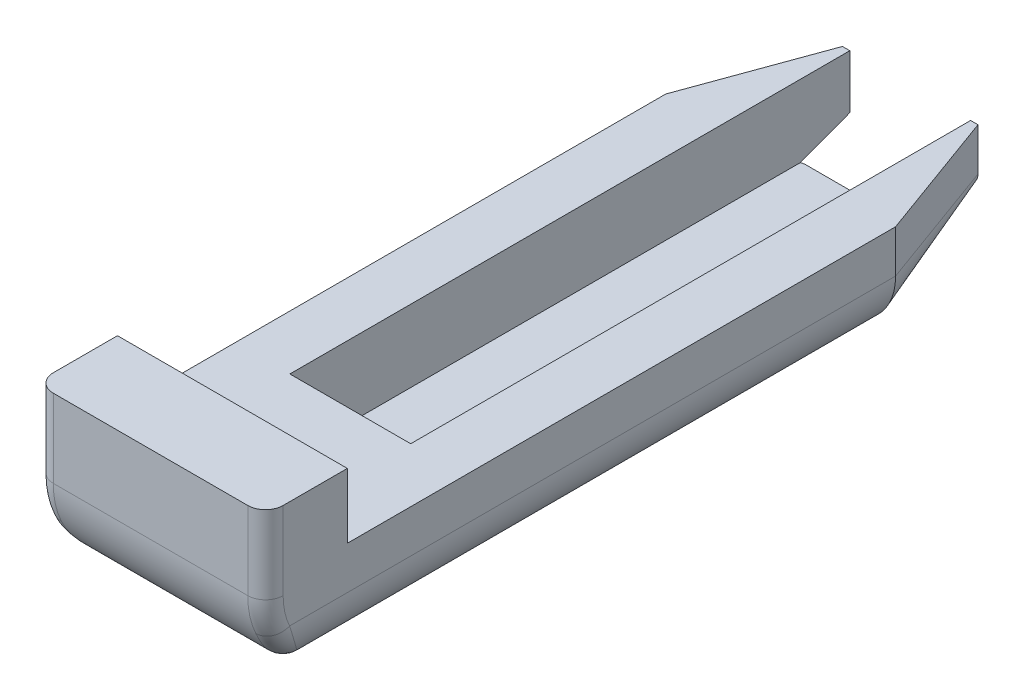
SolidWorks part; units mm, degrees
ref_plane "Front Plane" through (0, 0, 0) normal (0, 0, 1) x (1, 0, 0)
ref_plane "Top Plane" through (0, 0, 0) normal (0, 1, 0) x (1, 0, 0)
ref_plane "Right Plane" through (0, 0, 0) normal (1, 0, 0) x (0, 0, -1)
sketch "Sketch1" plane through (0, 0, 0) normal (0, 0, 1) x (1, 0, 0)
  line L1 (0, 0) -> (39, 0)
  line L2 (0, 0) -> (0, 17.25)
  line L3 (0, 17.25) -> (39, 17.25)
  line L4 (39, 0) -> (39, 17.25)
  line L5 (9.25, 17.25) -> (29.75, 17.25)
  line L6 (9.25, 17.25) -> (9.25, 5)
  line L7 (9.25, 5) -> (29.75, 5)
  line L8 (29.75, 17.25) -> (29.75, 5)
  dimension "D1" = 39
  dimension "D2" = 20.5
  dimension "D3" = 9.25
  dimension "D4" = 12.25
  dimension "D5" = 17.25
extrude "Boss-Extrude1" add sketch "Sketch1" along normal blind 95 contours L3 L8 L7 L6 L2 L1 L4 region at (0.4264, 8.625, 0)
sketch "Sketch2" plane through (0, 0, 95) normal (0, 0, 1) x (1, 0, 0)
  line L1 (0, 0) -> (39, 0)
  line L2 (0, 0) -> (0, 17.25)
  line L3 (0, 17.25) -> (39, 17.25)
  line L4 (39, 0) -> (39, 17.25)
extrude "Boss-Extrude2" add sketch "Sketch2" along normal blind 20
sketch "Sketch3" plane through (39, 0, 0) normal (1, 0, 0) x (0, 0, -1)
  line L1 (-115, 0) -> (-128.89, 0)
  line L2 (-115, 0) -> (-115, 28.25)
  line L3 (-115, 28.25) -> (-128.89, 28.25)
  line L4 (-128.89, 0) -> (-128.89, 28.25)
  dimension "D1" = 13.89
  dimension "D2" = 28.25
extrude "Boss-Extrude3" add sketch "Sketch3" against normal up to surface (39 mm away) up to face at (0, 8.625, 57.5)
fillet "Fillet1" radius 10 2 edges at (0, 0, 64.445) (39, 0, 64.445)
chamfer "Chamfer1" distance 8 angle 70 5 edges at (0, 13.625, 0) (2.9289, 2.9289, 0) (19.5, 0, 0) (36.0711, 2.9289, 0) (39, 13.625, 0) first distance on face at (19.5, 9.4858, 0)
sketch "Sketch4" plane through (39, 0, 0) normal (1, 0, 0) x (0, 0, -1)
  line L0 (-128.89, 0) -> (-128.89, 15)
  line L1 (-128.89, 28.25) -> (-128.89, 10) construction
  line L2 (-128.89, 15) -> (-113.89, 15)
  line L3 (-128.89, 0) -> (-113.89, 0)
  arc A0 (-128.89, 15) -> (-113.89, 0) centre (-113.89, 15) ccw
  line M3 (-128.89, 10) -> (-21.9798, 10)
  dimension "D1" = 15
  dimension "D2" = 15
extrude "Cut-Extrude1" cut sketch "Sketch4" against normal through all contours A0 L0 L3 M3 | A0 L3 L0 region at (39, 3.1126, 125.4462)
fillet "Fillet3" radius 3 6 edges at (2.155, 3.7987, 123.8665) (0, 12.4635, 128.674) (36.845, 3.7987, 123.8665) (39, 12.4635, 128.674) (0, 21.625, 128.89) (39, 21.625, 128.89)
